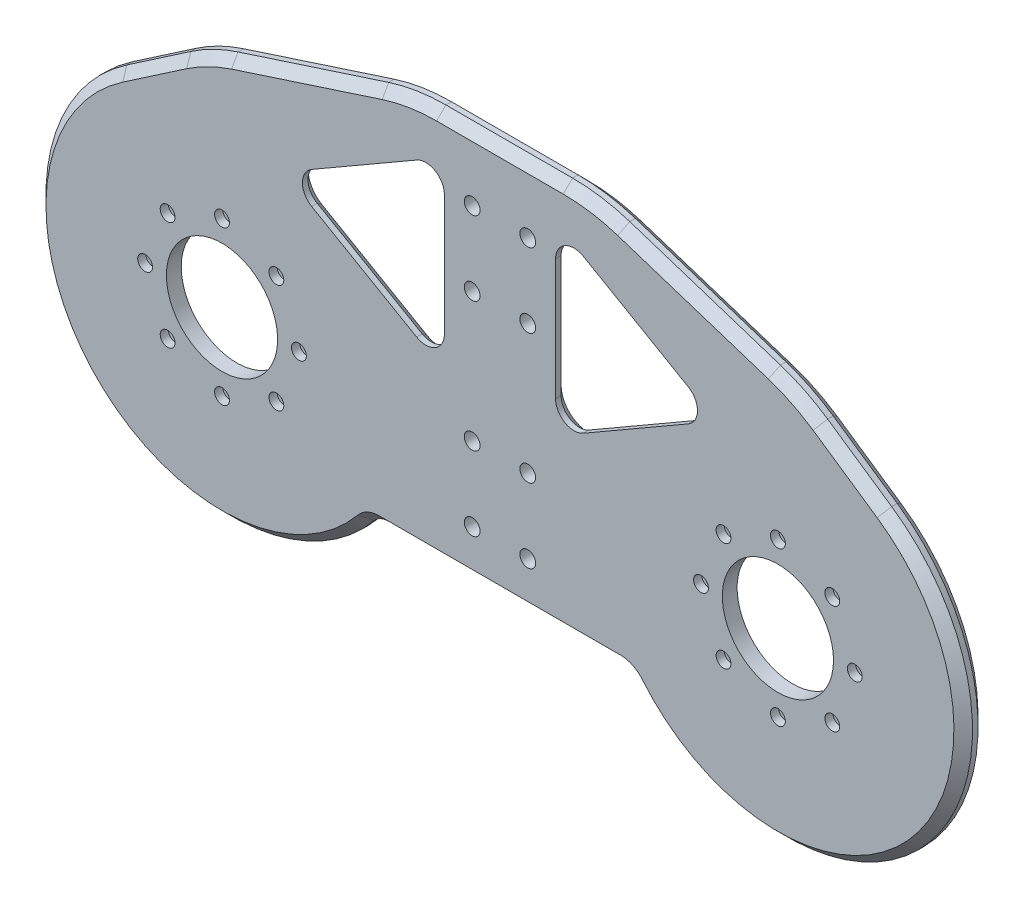
SolidWorks part; units mm, degrees
material "6061 合金"
ref_plane "前视基准面" through (0, 0, 0) normal (0, 0, 1) x (1, 0, 0)
ref_plane "上视基准面" through (0, 0, 0) normal (0, 1, 0) x (1, 0, 0)
ref_plane "右视基准面" through (0, 0, 0) normal (1, 0, 0) x (0, 0, -1)
other "Configuration Table"
sketch "草图1" plane through (0, 0, 0) normal (0, 0, 1) x (1, 0, 0)
  line L0 (0, 0) -> (0, 250) construction
  line L1 (0, 250) -> (769.4209, 0)
  line L3 (769.4209, 0) -> (0, 0)
  line L4 (-50, 404.7785) -> (-50, -103.66) construction
  line L5 (-869.4209, 0) -> (-100, 0)
  line L6 (-100, 250) -> (-869.4209, 0)
  line L7 (-100, 0) -> (-100, 250) construction
  line L8 (-100, 250) -> (0, 250)
  line L9 (-100, 0) -> (0, 0)
  circle A0 centre (100, 100) radius 85 construction
  circle A1 centre (100, 100) radius 30
  circle A2 centre (-200, 100) radius 85 construction
  circle A3 centre (-200, 100) radius 30
  dimension "D1" = 170
  dimension "D4" = 60
  dimension "D2" = 150
  dimension "D3" = 72
  dimension "D5" = 250
  dimension "D6" = 100
  dimension "D7" = 50
extrude "凸台-拉伸1" add sketch "草图1" along normal blind 8
sketch "草图8" plane through (0, 0, 8) normal (0, 0, 1) x (1, 0, 0)
  line L0 (100, 100) -> (100, 171.8517) construction
  line L1 (-50, 311.6242) -> (-50, -58.5513) construction
  line L2 (-200, 100) -> (-200, 171.8517) construction
  circle A0 centre (100, 100) radius 41.5 construction
  circle A1 centre (100, 141.5) radius 2.25
  circle A2 centre (129.3449, 129.3449) radius 2.25
  circle A3 centre (141.5, 100) radius 2.25
  circle A4 centre (129.3449, 70.6551) radius 2.25
  circle A5 centre (100, 58.5) radius 2.25
  circle A6 centre (70.6551, 70.6551) radius 2.25
  circle A7 centre (58.5, 100) radius 2.25
  circle A8 centre (70.6551, 129.3449) radius 2.25
  circle A9 centre (100, 100) radius 30 construction
  circle A10 centre (-200, 100) radius 30 construction
  circle A11 centre (-200, 100) radius 41.5 construction
  circle A12 centre (-170.6551, 129.3449) radius 2.25
  circle A13 centre (-158.5, 100) radius 2.25
  circle A14 centre (-170.6551, 70.6551) radius 2.25
  circle A15 centre (-200, 58.5) radius 2.25
  circle A16 centre (-229.3449, 70.6551) radius 2.25
  circle A17 centre (-241.5, 100) radius 2.25
  circle A18 centre (-229.3449, 129.3449) radius 2.25
  circle A19 centre (-200, 141.5) radius 2.25
  point P22 (100, 100)
  point P46 (-200, 100)
  point P47 (147.6218, 205.9135)
  point P48 (100, 100)
  dimension "D1" = 83
  dimension "D2" = 4.5
  dimension "D3" = 8
extrude "切除-拉伸5" cut sketch "草图8" against normal through all both and the other way through all
sketch "草图9" plane through (0, 0, 8) normal (0, 0, 1) x (1, 0, 0)
  line L0 (-50, 330.1155) -> (-50, -36.3961) construction
  circle A0 centre (-200, 100) radius 41.5 construction
  circle A1 centre (-200, 141.5) radius 4
  circle A2 centre (-170.6551, 129.3449) radius 4
  circle A3 centre (-158.5, 100) radius 4
  circle A4 centre (-170.6551, 70.6551) radius 4
  circle A5 centre (-200, 58.5) radius 4
  circle A6 centre (-229.3449, 70.6551) radius 4
  circle A7 centre (-241.5, 100) radius 4
  circle A8 centre (-229.3449, 129.3449) radius 4
  circle A9 centre (100, 100) radius 30 construction
  circle A10 centre (-200, 100) radius 30 construction
  circle A11 centre (100, 100) radius 41.5 construction
  circle A12 centre (129.3449, 129.3449) radius 4
  circle A13 centre (141.5, 100) radius 4
  circle A14 centre (129.3449, 70.6551) radius 4
  circle A15 centre (100, 58.5) radius 4
  circle A16 centre (70.6551, 70.6551) radius 4
  circle A17 centre (58.5, 100) radius 4
  circle A18 centre (70.6551, 129.3449) radius 4
  circle A19 centre (100, 141.5) radius 4
  point P22 (-200, 100)
  point P45 (100, 100)
  point P46 (100, 100)
  dimension "D1" = 8
  dimension "D2" = 8
extrude "切除-拉伸6" cut sketch "草图9" against normal blind 4.4
fillet "圆角1" radius 100 2 edges at (-869.4209, 0, 4) (769.4209, 0, 4)
sketch "草图12" plane through (0, 0, 0) normal (0, 0, -1) x (-1, 0, 0)
  line L0 (50, 285.9765) -> (50, -67.6003) construction
  line L1 (238.0457, 0) -> (-138.0457, 0) construction
  line L3 (-20, 40) -> (120, 40)
  line L6 (200, 0) -> (-100, 0)
  arc A0 (120, 40) -> (200, 0) centre (200, 100) ccw
  circle A2 centre (200, 100) radius 30 construction
  circle A3 centre (-100, 100) radius 30 construction
  arc A7 (-100, 0) -> (-20, 40) centre (-100, 100) ccw
  dimension "D1" = 40
extrude "切除-拉伸7" cut sketch "草图12" against normal blind 83
sketch "草图13" plane through (0, 0, 8) normal (0, 0, 1) x (1, 0, 0)
  line L0 (-238.0457, 0) -> (-200, 0) construction
  line L1 (-238.0457, 0) -> (-200, 0)
  line L2 (-50, 304.265) -> (-50, -26.0703) construction
  line L3 (-210, 214.2588) -> (-256.3883, 182.5854)
  line L4 (-100, 250) -> (-268.9474, 195.1057) construction
  line L5 (-210, 214.2588) -> (-268.9474, 195.1057)
  line L6 (110, 214.2588) -> (168.9474, 195.1057)
  line L7 (110, 214.2588) -> (156.3883, 182.5854)
  line L8 (138.0457, 0) -> (100, 0)
  arc A0 (-256.3883, 182.5854) -> (-200, 0) centre (-200, 100) ccw
  circle A1 centre (100, 100) radius 30 construction
  circle A2 centre (-200, 100) radius 30 construction
  arc A3 (-268.9474, 195.1057) -> (-238.0457, 0) centre (-238.0457, 100) ccw construction
  arc A4 (-268.9474, 195.1057) -> (-238.0457, 0) centre (-238.0457, 100) ccw
  arc A5 (168.9474, 195.1057) -> (138.0457, 0) centre (138.0457, 100) cw
  arc A6 (156.3883, 182.5854) -> (100, 0) centre (100, 100) cw
  dimension "D1" = 160
extrude "切除-拉伸8" cut sketch "草图13" against normal blind 83
fillet "圆角3" radius 100 4 edges at (110, 214.2588, 4) (0, 250, 4) (-100, 250, 4) (-210, 214.2588, 4)
fillet "圆角4" radius 10 2 edges at (20, 40, 4) (-120, 40, 4)
sketch "草图14" plane through (0, 0, 8) normal (0, 0, 1) x (1, 0, 0)
  line L0 (-50, 283.8941) -> (-50, -28.6031) construction
  line L1 (-115.1472, 40) -> (15.1472, 40) construction
  circle A0 centre (-200, 100) radius 30 construction
  circle A1 centre (100, 100) radius 30 construction
  circle A2 centre (-35, 65) radius 4.25
  circle A3 centre (-35, 105) radius 4.25
  circle A4 centre (-35, 175) radius 4.25
  circle A5 centre (-35, 215) radius 4.25
  circle A6 centre (-65, 215) radius 4.25
  circle A7 centre (-65, 175) radius 4.25
  circle A8 centre (-65, 105) radius 4.25
  circle A9 centre (-65, 65) radius 4.25
  point P14 (0, 0)
  point P15 (0, 0)
  point P16 (-5.3575, 109.2925)
  point P17 (0, 0)
  dimension "D6" = 8.5
  dimension "D1" = 40
  dimension "D2" = 15
  dimension "D3" = 40
  dimension "D4" = 70
  dimension "D5" = 15
  dimension "D7" = 25
extrude "切除-拉伸9" cut sketch "草图14" against normal blind 83
sketch "草图15" plane through (0, 0, 0) normal (0, 0, -1) x (-1, 0, 0)
  line L0 (50, 291.1692) -> (50, -23.3122) construction
  line L1 (55, 50) -> (128.193, 50)
  line L2 (55, 240) -> (98.4162, 240)
  line L3 (98.4162, 240) -> (197.0868, 207.94)
  line L4 (197.0868, 207.94) -> (249.3398, 172.2623)
  line L5 (115.1472, 40) -> (-15.1472, 40) construction
  line L6 (15.8384, 250) -> (84.1616, 250) construction
  line L7 (115.0633, 245.1057) -> (196.3588, 218.6911) construction
  line L8 (221.8454, 206.1709) -> (256.3883, 182.5854) construction
  line L9 (55, 240) -> (55, 50)
  line L10 (45, 240) -> (45, 50)
  line L11 (-97.0868, 207.94) -> (-149.3398, 172.2623)
  line L12 (1.5838, 240) -> (-97.0868, 207.94)
  line L13 (45, 240) -> (1.5838, 240)
  line L14 (45, 50) -> (-28.193, 50)
  line L21 (-15.0633, 245.1057) -> (-96.3588, 218.6911)
  line L22 (-121.8454, 206.1709) -> (-156.3883, 182.5854)
  line L23 (-15.1472, 40) -> (115.1472, 40)
  line L24 (256.3883, 182.5854) -> (221.8454, 206.1709)
  line L25 (196.3588, 218.6911) -> (115.0633, 245.1057)
  line L26 (84.1616, 250) -> (15.8384, 250)
  line L27 (-15.0633, 245.1057) -> (-96.3588, 218.6911)
  line L28 (-121.8454, 206.1709) -> (-156.3883, 182.5854)
  line L29 (-15.1472, 40) -> (115.1472, 40)
  line L30 (256.3883, 182.5854) -> (221.8454, 206.1709)
  line L31 (196.3588, 218.6911) -> (115.0633, 245.1057)
  line L32 (84.1616, 250) -> (15.8384, 250)
  circle A0 centre (200, 100) radius 87.5 construction
  circle A1 centre (200, 100) radius 30 construction
  circle A2 centre (-100, 100) radius 30 construction
  arc A3 (128.193, 50) -> (249.3398, 172.2623) centre (200, 100) ccw
  circle A4 centre (-100, 100) radius 87.5 construction
  arc A5 (-28.193, 50) -> (-149.3398, 172.2623) centre (-100, 100) cw
  arc A14 (-96.3588, 218.6911) -> (-121.8454, 206.1709) centre (-65.4571, 123.5855) ccw
  arc A15 (-156.3883, 182.5854) -> (-22.8611, 36.3636) centre (-100, 100) ccw
  arc A16 (-15.1472, 40) -> (-22.8611, 36.3636) centre (-15.1472, 30) ccw
  arc A17 (122.8611, 36.3636) -> (115.1472, 40) centre (115.1472, 30) ccw
  arc A18 (122.8611, 36.3636) -> (256.3883, 182.5854) centre (200, 100) ccw
  arc A19 (221.8454, 206.1709) -> (196.3588, 218.6911) centre (165.4571, 123.5855) ccw
  arc A20 (115.0633, 245.1057) -> (84.1616, 250) centre (84.1616, 150) ccw
  arc A21 (15.8384, 250) -> (-15.0633, 245.1057) centre (15.8384, 150) ccw
  arc A22 (-96.3588, 218.6911) -> (-121.8454, 206.1709) centre (-65.4571, 123.5855) ccw
  arc A23 (-156.3883, 182.5854) -> (-22.8611, 36.3636) centre (-100, 100) ccw
  arc A24 (-15.1472, 40) -> (-22.8611, 36.3636) centre (-15.1472, 30) ccw
  arc A25 (122.8611, 36.3636) -> (115.1472, 40) centre (115.1472, 30) ccw
  arc A26 (122.8611, 36.3636) -> (256.3883, 182.5854) centre (200, 100) ccw
  arc A27 (221.8454, 206.1709) -> (196.3588, 218.6911) centre (165.4571, 123.5855) ccw
  arc A28 (115.0633, 245.1057) -> (84.1616, 250) centre (84.1616, 150) ccw
  arc A29 (15.8384, 250) -> (-15.0633, 245.1057) centre (15.8384, 150) ccw
  dimension "D1" = 175
  dimension "D2" = 10
  dimension "D3" = 10
  dimension "D4" = 10
  dimension "D5" = 5
  dimension "D6" = 0
extrude "凸台-拉伸2" add sketch "草图15" along normal blind 5
sketch "草图16" plane through (0, 0, 0) normal (0, 0, -1) x (-1, 0, 0)
  line L0 (80, 230) -> (80, 130)
  line L1 (80, 130) -> (166.6025, 180)
  line L2 (166.6025, 180) -> (80, 230)
  line L3 (50, 302.4124) -> (50, -31.91) construction
  line L4 (84.1616, 250) -> (15.8384, 250) construction
  line L5 (-66.6025, 180) -> (20, 230)
  line L6 (20, 130) -> (-66.6025, 180)
  line L7 (20, 230) -> (20, 130)
  circle A0 centre (200, 100) radius 30 construction
  circle A1 centre (-100, 100) radius 30 construction
  dimension "D1" = 30
  dimension "D2" = 20
  dimension "D3" = 100
  dimension "D4" = 100
  dimension "D5" = 100
extrude "切除-拉伸10" cut sketch "草图16" against normal blind 69
fillet "圆角5" radius 10 16 edges at (97.0868, 207.94, -2.5) (-1.5838, 240, -2.5) (28.193, 50, -2.5) (-45, 50, -2.5) (-45, 240, -2.5) (-98.4162, 240, -2.5) (-197.0868, 207.94, -2.5) (-128.193, 50, -2.5) (-55, 50, -2.5) (-55, 240, -2.5) (-166.6025, 180, 4) (-80, 130, 4) (-80, 230, 4) (-20, 230, 4) (66.6025, 180, 4) (-20, 130, 4)
chamfer "倒角1" distance 5 angle 45 28 edges at (-119.4112, 39.0453, 8) (-50, 40, 8) (-273.8434, 32.5674, 8) (19.4112, 39.0453, 8) (-239.1169, 194.3782, 8) (173.8434, 32.5674, 8) (-209.5488, 213.3403, 8) (139.1169, 194.3782, 8) (-155.711, 231.8984, 8) (109.5488, 213.3403, 8) (-99.805, 248.7688, 8) (55.711, 231.8984, 8) (-50, 250, 8) (-0.195, 248.7688, 8) (-50, 40, -5) (-119.4112, 39.0453, -5) (19.4112, 39.0453, -5) (-273.8434, 32.5674, -5) (173.8434, 32.5674, -5) (-239.1169, 194.3782, -5) (139.1169, 194.3782, -5) (-209.5488, 213.3403, -5) (109.5488, 213.3403, -5) (-155.711, 231.8984, -5) (55.711, 231.8984, -5) (-99.805, 248.7688, -5) (-0.195, 248.7688, -5) (-50, 250, -5)
chamfer "倒角2" distance 5 angle 45 12 edges at (-85, 221.3397, 0) (-80, 180, 0) (-123.3013, 205, 0) (-85, 138.6603, 0) (-156.6025, 180, 0) (-123.3013, 155, 0) (-15, 221.3397, 0) (23.3013, 205, 0) (-20, 180, 0) (56.6025, 180, 0) (-15, 138.6603, 0) (23.3013, 155, 0)
